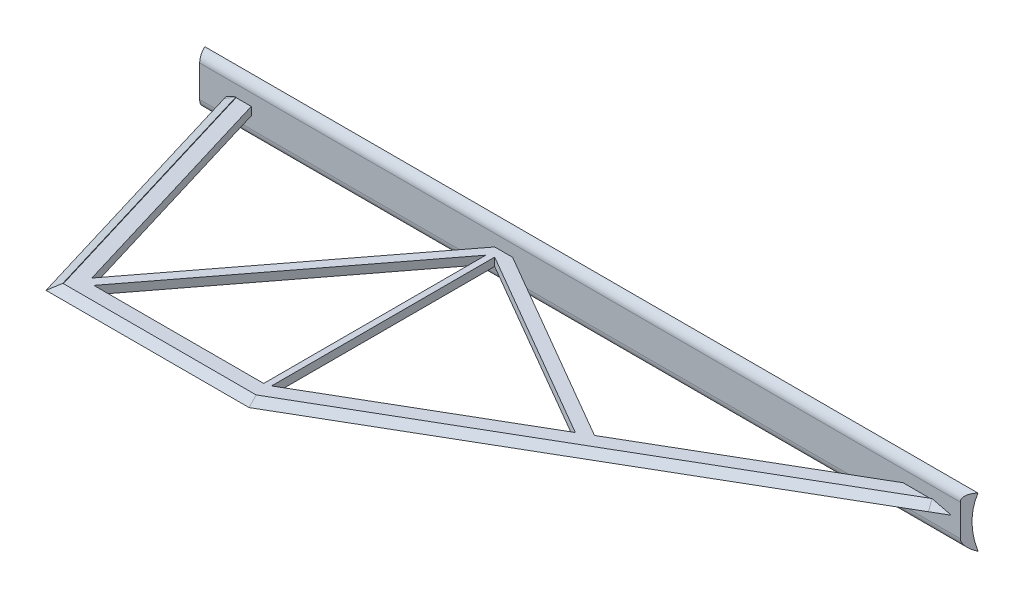
SolidWorks part; units mm, degrees
material "6061-T6 (SS)"
ref_plane "Front Plane" through (0, 0, 0) normal (0, 0, 1) x (1, 0, 0)
ref_plane "Top Plane" through (0, 0, 0) normal (0, 1, 0) x (1, 0, 0)
ref_plane "Right Plane" through (0, 0, 0) normal (1, 0, 0) x (0, 0, -1)
sketch "CS path" plane through (0, 0, 0) normal (0, 1, 0) x (1, 0, 0)
  line L0 (-228.6, 0) -> (228.6, 0) construction
  line L1 (-115.8864, -163.068) -> (0, 0) construction
  line L2 (-52.3864, -163.068) -> (228.6, 0)
  line L3 (-228.6, 0) -> (-235.9387, 24.3167) construction
  line L4 (228.6, 0) -> (294.5056, 38.2477) construction
  line L5 (228.6, 0) -> (294.5056, 38.2477)
  line L6 (-179.3864, -163.068) -> (-52.3864, -163.068)
  line L8 (-228.6, 0) -> (-235.9387, 24.3167)
  line L9 (-179.3864, -163.068) -> (-228.6, 0) construction
  line L12 (-179.3864, -163.068) -> (-228.6, 0)
  dimension "D1" = 163.068
  dimension "D2" = 127
  dimension "D3" = 457.2
  dimension "D4" = 54.6
  dimension "D5" = 0
  dimension "D6" = 25.4
  dimension "D7" = 76.2
sketch "Sketch8" plane through (0, 0, 0) normal (1, 0, 0) x (0, 0, -1)
  line L0 (0, 0) -> (82.804, 0) construction
  line L1 (82.804, 0) -> (-43.02, 26.7447) construction
  line L2 (82.804, 0) -> (-44.9942, -27.1644) construction
  line L3 (4.8299, 16.5739) -> (0, 17.6005)
  line L4 (4.8299, -16.5739) -> (0, -17.6005)
  line L5 (0, 17.6005) -> (0, -17.6005)
  line L6 (3.175, 0) -> (86.995, 0) construction
  arc A0 (4.8299, 16.5739) -> (4.8299, -16.5739) centre (86.995, 0) ccw
  dimension "D1" = 12
  dimension "D2" = 12
extrude "Boss-Extrude3" add sketch "Sketch8" along normal blind 254 and the other way blind 254 separate body
ref_plane "Plane7" through (0, 17.6005, 0) normal (0, -1, 0) x (1, 0, 0)
ref_plane "Plane8" through (294.5056, 0, -38.2477) normal (0.8649, 0, -0.5019) x (-0.5019, 0, -0.8649)
sketch "Sketch9" plane through (294.5056, 0, -38.2477) normal (0.8649, 0, -0.5019) x (-0.5019, 0, -0.8649)
  line L1 (0, 3.175) -> (9.525, 3.175)
  line L3 (0, -3.175) -> (9.525, -3.175)
  line L4 (9.525, 3.175) -> (9.525, -3.175)
  line L6 (0, 3.175) -> (-6.35, 0)
  line L7 (-6.35, 0) -> (0, -3.175)
  dimension "D3" = 9.525
sweep "Sweep2" add profiles "Sketch9" path "CS path"
sketch "Sketch11" plane through (-254, 0, 0) normal (-1, 0, 0) x (0, 0, 1)
  line L0 (-55.6299, -16.5739) -> (-55.6299, 16.5739)
  line L1 (-4.8299, 16.5739) -> (-55.6299, 16.5739)
  line L2 (-4.8299, -16.5739) -> (-55.6299, -16.5739)
  arc A0 (-4.8299, 16.5739) -> (-4.8299, -16.5739) centre (-86.995, 0) cw
  dimension "D1" = 50.8
extrude "Cut-Extrude1" cut sketch "Sketch11" against normal blind 762
sketch "Sketch12" plane through (0, 3.175, 0) normal (0, 1, 0) x (1, 0, 0)
  line L0 (-54.9501, -153.543) -> (-54.9501, 0) construction
  line L1 (-254, 0) -> (254, 0) construction
  line L2 (-54.9501, 0) -> (-172.3117, -153.543) construction
  line L3 (77.3368, -76.7715) -> (-54.9501, 0) construction
  line L4 (-58.7261, 0) -> (-173.3806, -150.0013)
  line L6 (-52.9501, -152.3823) -> (-52.9501, -5.7855)
  line L7 (-218.6507, 0) -> (-172.3117, -153.543)
  line L8 (-172.3117, -153.543) -> (-54.9501, -153.543)
  line L9 (-54.9501, -153.543) -> (209.6236, 0)
  line L10 (209.6236, 0) -> (-218.6507, 0)
  line L11 (-56.9501, -153.543) -> (-56.9501, -7.5567)
  line L12 (81.3213, -74.4591) -> (-46.981, 0)
  line L13 (73.3522, -79.0839) -> (-52.9501, -5.7855)
  line L14 (79.3445, -73.3119) -> (-52.9423, 3.4596) construction
  line L15 (-57.3335, 1.8218) -> (-174.6952, -151.7212) construction
  line L16 (-56.9501, -7.5567) -> (-168.5357, -153.543)
  line L18 (-52.9501, -153.543) -> (-52.9501, 0) construction
  line L19 (75.329, -80.2311) -> (-56.9578, -3.4596) construction
  line L21 (-56.9501, -153.543) -> (-56.9501, 0) construction
  line M9 (-172.3117, -153.543) -> (-218.6507, 0)
  dimension "D3" = 2
  dimension "D1" = 3
  dimension "D4" = 2
  dimension "D5" = 4
  dimension "D6" = 4
extrude "Boss-Extrude4" add sketch "Sketch12" against normal blind 6.35 contours L8 L9 L10 M9 region at (-52.8535, 3.175, 2.974)
fillet "Fillet3" radius 6.35 2 edges at (0, -17.6005, 0) (0, 17.6005, 0)
ref_plane "Plane9" through (0, 16.5739, 0) normal (0, 1, 0) x (1, 0, 0)
sketch "Sketch13" plane through (0, 16.5739, 0) normal (0, 1, 0) x (1, 0, 0)
  line L0 (-254, 4.8299) -> (-254, 0)
  line L1 (254, 0) -> (-254, 0) construction
  line L2 (-254, 4.8299) -> (-254, 0) construction
  line L3 (-254, 0) -> (-252.5427, 0)
  line L4 (-252.5427, 0) -> (-254, 4.8299)
  line L5 (254, 4.8299) -> (254, 0)
  line L6 (254, 0) -> (247.2036, 0)
  line L7 (247.2036, 0) -> (254, 4.8299)
  line L9 (-184.1029, -169.418) -> (-234.6792, -1.8347) construction
  line L11 (-254, 4.8299) -> (254, 4.8299) construction
  dimension "D1" = 4.8299
  dimension "D2" = 73.21
  dimension "D3" = 54.6
  dimension "D4" = 73.206
extrude "Cut-Extrude2" cut sketch "Sketch13" against normal blind 50.8
sketch "Sketch14" plane through (0, 3.175, 0) normal (0, 1, 0) x (1, 0, 0)
  line L0 (228.6, 0) -> (-228.6, 0)
  line L1 (-228.6, 0) -> (-179.3864, -163.068)
  line L2 (-179.3864, -163.068) -> (-52.3864, -163.068)
  line L3 (-52.3864, -163.068) -> (228.6, 0)
extrude "Cut-Extrude3" cut sketch "Sketch14" against normal blind 0.508
mirror "Mirror1" about plane through (0, 0, 0) normal (0, 1, 0) of "Cut-Extrude3"
